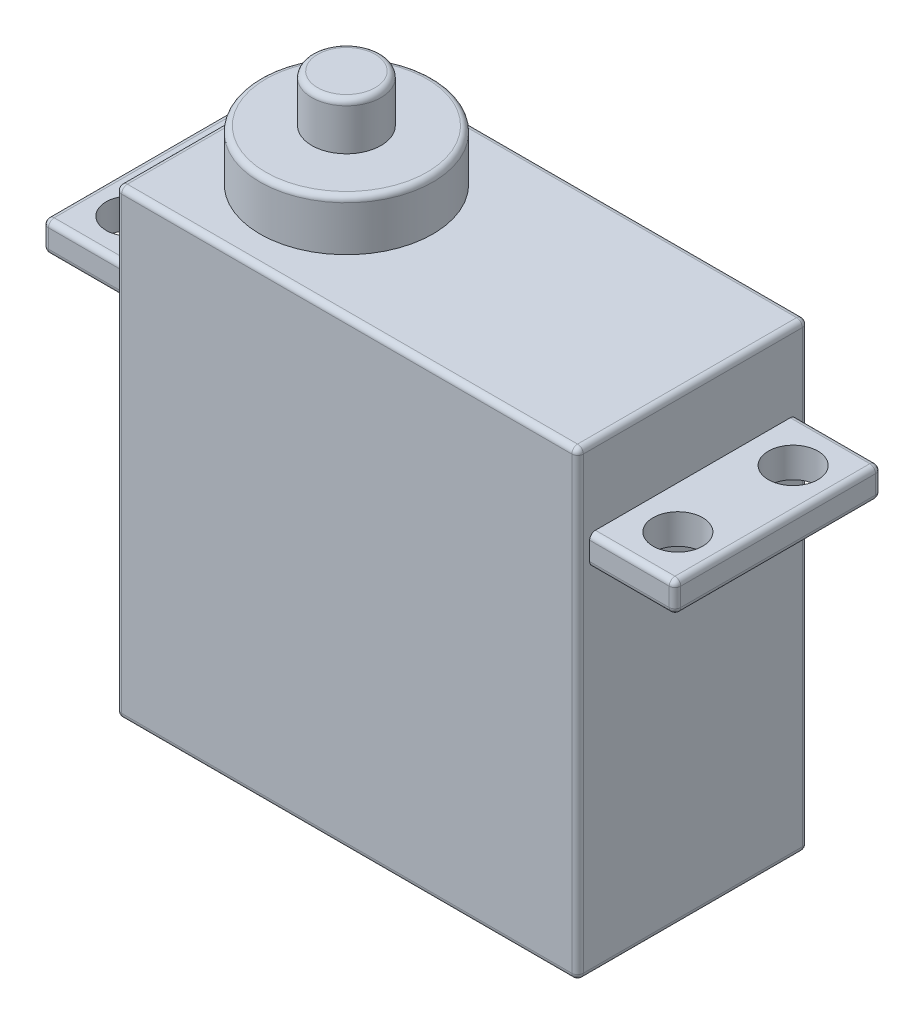
SolidWorks part; units mm, degrees
ref_plane "Front Plane" through (0, 0, 0) normal (0, 0, 1) x (1, 0, 0)
ref_plane "Top Plane" through (0, 0, 0) normal (0, 1, 0) x (1, 0, 0)
ref_plane "Right Plane" through (0, 0, 0) normal (1, 0, 0) x (0, 0, -1)
sketch "Sketch1" plane through (0, 0, 0) normal (0, 1, 0) x (1, 0, 0)
  line L0 (-20.025, 8.95) -> (-27.425, 8.95)
  line L1 (-20.025, -10) -> (20.025, -10)
  line L2 (-20.025, -10) -> (-20.025, 10)
  line L3 (-20.025, 10) -> (20.025, 10)
  line L4 (20.025, -10) -> (20.025, 10)
  line L5 (-20.025, -10) -> (20.025, 10) construction
  line L6 (-20.025, 10) -> (20.025, -10) construction
  line L7 (-20.025, -8.95) -> (-27.425, -8.95)
  line L8 (-27.425, -8.95) -> (-27.425, 8.95)
  line L9 (0, -254.9009) -> (0, 12490.144) construction
  line L10 (-23.725, 5) -> (-23.725, -5) construction
  line L11 (-20.025, -8.95) -> (-20.025, 8.95)
  line L12 (-27.425, -8.95) -> (-27.425, 8.95)
  line L13 (-20.025, -8.95) -> (-20.025, 8.95)
  line L14 (23.725, 5) -> (23.725, -5) construction
  line L15 (20.025, -8.95) -> (20.025, 8.95)
  line L16 (27.425, -8.95) -> (27.425, 8.95)
  line L17 (20.025, -8.95) -> (20.025, 8.95)
  line L18 (27.425, -8.95) -> (27.425, 8.95)
  line L19 (20.025, -8.95) -> (27.425, -8.95)
  line L20 (20.025, 8.95) -> (27.425, 8.95)
  circle A0 centre (-23.725, 5) radius 2.15
  circle A1 centre (-23.725, -5) radius 2.15
  circle A2 centre (23.725, -5) radius 2.15
  circle A3 centre (23.725, 5) radius 2.15
  circle A4 centre (-10.025, 0) radius 7.5
  circle A5 centre (-10.025, 0) radius 3
  point P0 (0, 0)
  point P14 (-23.725, 0)
  point P15 (-27.425, 0)
  point P16 (-20.025, 0)
  point P21 (-23.725, 8.95)
  dimension "D2" = 4.3
  dimension "D7" = 15
  dimension "D9" = 6
  dimension "D1" = 40.05
  dimension "D3" = 17.9
  dimension "D4" = 10
  dimension "D5" = 20
  dimension "D6" = 7.4
  dimension "D8" = 10
extrude "Boss-Extrude1" add sketch "Sketch1" against normal blind 40 contours L1 L4 L3 L2 A4 | A4 A5 | A5 region at (2.8377, 0, 0) region at (-17.3129, 0, 0) region at (-10.025, 0, 0)
extrude "Boss-Extrude2" add sketch "Sketch1<3>" against normal blind 2.6 from offset 6.75 contours L8 L7 L2 L0 A1 A0 | L20 L4 L19 L16 A2 A3 region at (-23.725, 0, 0) region at (23.725, 0, 0) offset against normal yes
sketch "Sketch1<3>" plane through (0, 0, 0) normal (0, 1, 0) x (1, 0, 0) same geometry as "Sketch1"
extrude "Boss-Extrude3" add sketch "Sketch1<4>" along normal blind 4.4 contours A4 A5 | A5 region at (-17.3129, 0, 0) region at (-10.025, 0, 0)
sketch "Sketch1<4>" plane through (0, 0, 0) normal (0, 1, 0) x (1, 0, 0) same geometry as "Sketch1"
extrude "Boss-Extrude4" add sketch "Sketch1<5>" along normal blind 4.1 from surface contours A5 region at (-10.025, 0, 0) starting at face at (-10.025, 4.4, 7.5)
sketch "Sketch1<5>" plane through (0, 0, 0) normal (0, 1, 0) x (1, 0, 0) same geometry as "Sketch1"
fillet "Fillet1" radius 0.5 30 edges at (27.425, -8.05, -8.95) (27.425, -9.35, 0) (27.425, -8.05, 8.95) (27.425, -6.75, 0) (-20.025, -20, -10) (20.025, -20, -10) (0, 0, -10) (20.025, -40, 0) (0, -40, -10) (-20.025, -40, 0) (20.025, -20, 10) (0, -40, 10) (-20.025, -20, 10) (0, 0, 10) (23.725, -9.35, -8.95) (23.725, -6.75, -8.95) (23.725, -9.35, 8.95) (23.725, -6.75, 8.95) (-23.725, -9.35, 8.95) (-27.425, -8.05, 8.95) (-27.425, -8.05, -8.95) (-23.725, -9.35, -8.95) (-27.425, -9.35, 0) (-23.725, -6.75, 8.95) (-27.425, -6.75, 0) (-23.725, -6.75, -8.95) (-10.025, 8.5, 3) (-10.025, 4.4, 7.5) (20.025, 0, 0) (-20.025, 0, 0)
